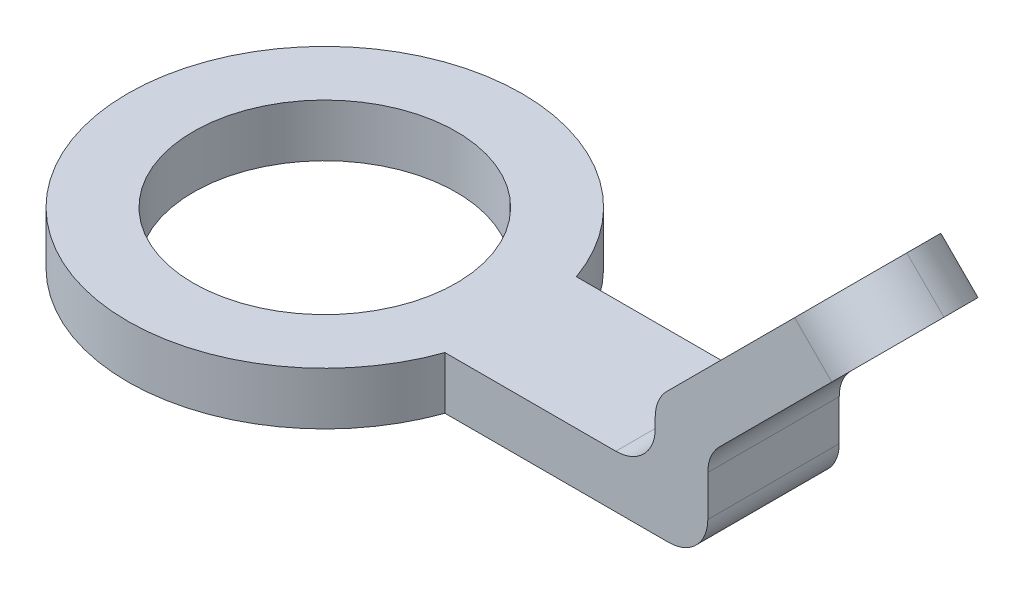
SolidWorks part; units mm, degrees
ref_plane "Front Plane" through (0, 0, 0) normal (0, 0, 1) x (1, 0, 0)
ref_plane "Top Plane" through (0, 0, 0) normal (0, 1, 0) x (1, 0, 0)
ref_plane "Right Plane" through (0, 0, 0) normal (1, 0, 0) x (0, 0, -1)
sketch "Sketch2" plane through (0, 0, 0) normal (0, 1, 0) x (1, 0, 0)
  line L0 (0, 0) -> (34.1421, 0) construction
  line L1 (34.1421, 5) -> (34.1421, -5)
  line L2 (34.1421, -5) -> (14.1421, -5)
  line L3 (34.1421, 5) -> (14.1421, 5)
  arc A0 (14.1421, 5) -> (14.1421, -5) centre (0, 0) ccw
  circle A1 centre (0, 0) radius 10
  dimension "D1" = 30
  dimension "D5" = 20
  dimension "D2" = 5
  dimension "D3" = 5
  dimension "D4" = 20
extrude "Boss-Extrude1" add sketch "Sketch2" along normal blind 4
sketch "Sketch3" plane through (0, 0, 5) normal (0, 0, 1) x (1, 0, 0)
  line L0 (34.1421, 4) -> (34.1421, 7.3431)
  line L1 (34.1421, 7.3431) -> (47.1127, 20.3137)
  line L2 (47.1127, 20.3137) -> (44.2843, 23.1421)
  line L3 (44.2843, 23.1421) -> (30.1421, 9)
  line L4 (30.1421, 9) -> (30.1421, 4)
  line L5 (14.1421, 4) -> (34.1421, 4) construction
  line L6 (30.1421, 4) -> (34.1421, 4)
  dimension "D1" = 4
  dimension "D2" = 4
  dimension "D3" = 135
  dimension "D4" = 5
  dimension "D5" = 20
extrude "Boss-Extrude2" add sketch "Sketch3" against normal blind 10
sketch "Sketch4" plane through (0, 0, 0) normal (0, -1, 0) x (1, 0, 0)
  circle A0 centre (0, 0) radius 12
  circle A1 centre (0, 0) radius 13
  dimension "D1" = 24
  dimension "D2" = 26
extrude "Boss-Extrude3" add sketch "Sketch4" along normal blind 1
fillet "Fillet1" radius 5 2 edges at (45.6985, 21.7279, -5) (45.6985, 21.7279, 5)
sketch "Sketch5" plane through (10.5711, -10.5711, 0) normal (-0.7071, 0.7071, 0) x (0.7071, 0.7071, 0)
  circle A0 centre (42.6777, 0) radius 2.5
  dimension "D1" = 5
hole_wizard "M3 Clearance Hole1" positions "Sketch6" profile "Sketch7" hole size "M3" standard "ANSI Metric" end condition through all
sketch "Sketch6" plane through (10.5711, -10.5711, 0) normal (-0.7071, 0.7071, 0) x (0.7071, 0.7071, 0)
  point P0 (42.6777, 0)
sketch "Sketch7" plane through (40.7487, 19.6066, 0) normal (0, 0, 1) x (-0.7071, -0.7071, 0)
  line L0 (0, 0) -> (0, 19.0711)
  line L1 (0, 19.0711) -> (1.8, 19.0711)
  line L2 (1.8, 19.0711) -> (1.8, 0)
  line L5 (1.8, 0) -> (0, 0)
  line L11 (0, -6.35) -> (0, 107.95) construction
  dimension "Thru Hole Dia." = 3.6
  dimension "Thru Hole Depth" = 19.0711
fillet "Fillet2" radius 3 4 edges at (34.1421, 7.3431, 0) (30.1421, 9, 0) (34.1421, 0, 0) (30.1421, 4, 0)
